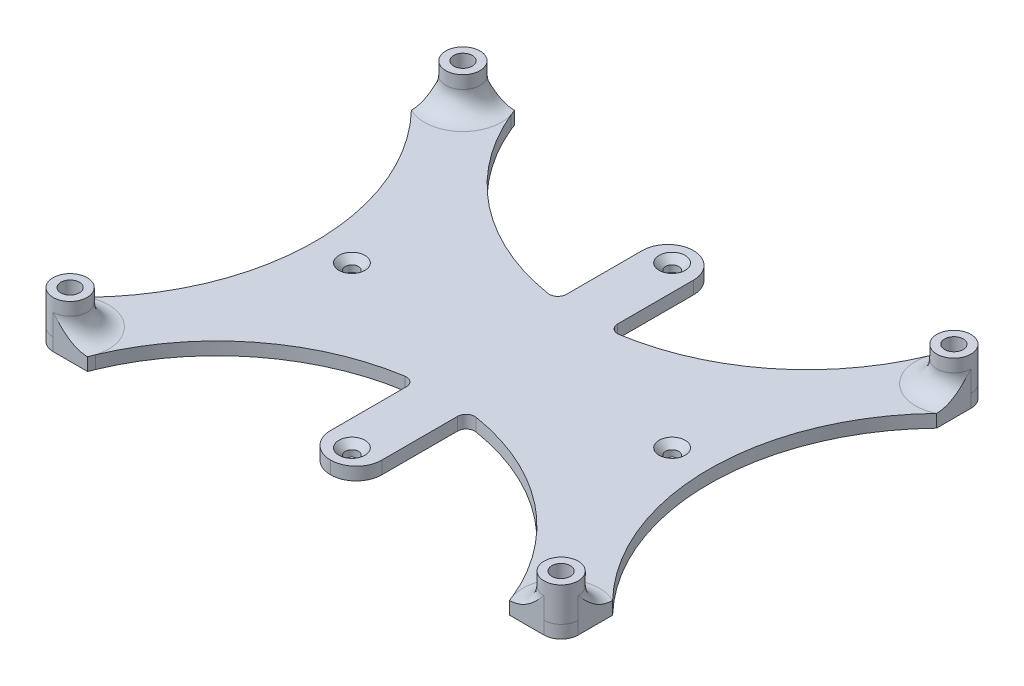
SolidWorks part; units mm, degrees
ref_plane "Alzado" through (0, 0, 0) normal (0, 0, 1) x (1, 0, 0)
ref_plane "Planta" through (0, 0, 0) normal (0, 1, 0) x (1, 0, 0)
ref_plane "Vista lateral" through (0, 0, 0) normal (1, 0, 0) x (0, 0, -1)
sketch "Croquis1" plane through (0, 0, 0) normal (0, 1, 0) x (1, 0, 0)
  line L1 (0, 0) -> (123, 0)
  line L2 (0, 0) -> (0, 100)
  line L3 (0, 100) -> (123, 100)
  line L4 (123, 0) -> (123, 100)
  dimension "D1" = 123
  dimension "D2" = 100
extrude "Saliente-Extruir1" add sketch "Croquis1" along normal blind 3
sketch "Croquis2" plane through (0, 3, 0) normal (0, 1, 0) x (1, 0, 0)
  line L0 (61.5, 100) -> (61.5, 0) construction
  line L1 (123, 100) -> (0, 100) construction
  line L2 (0, 0) -> (123, 0) construction
  line L3 (123, 0) -> (123, 100) construction
  line L4 (4, 4) -> (119, 4) construction
  line L5 (4, 4) -> (4, 96) construction
  line L6 (4, 96) -> (119, 96) construction
  line L7 (119, 4) -> (119, 96) construction
  line L8 (4, 4) -> (119, 96) construction
  line L9 (4, 96) -> (119, 4) construction
  circle A0 centre (4, 96) radius 4
  circle A1 centre (4, 4) radius 4
  circle A2 centre (119, 4) radius 4
  circle A3 centre (119, 96) radius 4
  point P6 (61.5, 50)
  dimension "D1" = 115
  dimension "D2" = 92
extrude "Saliente-Extruir2" add sketch "Croquis2" along normal blind 8
sketch "Croquis3" plane through (0, 11, 0) normal (0, 1, 0) x (1, 0, 0)
  circle A0 centre (4, 4) radius 4 construction
  circle A1 centre (4, 96) radius 4
  circle A2 centre (4, 96) radius 4
  arc A3 (123, 4) -> (119, 0) centre (119, 4) ccw construction
  arc A4 (119, 100) -> (123, 96) centre (119, 96) ccw construction
  circle A5 centre (4, 4) radius 4
  arc A6 (123, 4) -> (119, 0) centre (119, 4) ccw
  arc A7 (119, 100) -> (123, 96) centre (119, 96) ccw
  circle A8 centre (4, 96) radius 2.175
  circle A9 centre (119, 96) radius 2.175
  circle A10 centre (119, 4) radius 2.175
  circle A11 centre (4, 4) radius 2.175
  dimension "D2" = 4.35
  dimension "D1" = 0
extrude "Cortar-Extruir1" cut sketch "Croquis3" against normal blind 4.5 contours A8 | A9 | A10 | A11 region at (4, 11, -96) region at (119, 11, -96) region at (119, 11, -4) region at (4, 11, -4)
fillet "Redondeo1" radius 4 4 edges at (0, 1.5, -100) (123, 1.5, -100) (123, 1.5, 0) (0, 1.5, 0)
fillet "Redondeo2" radius 5 4 edges at (116.1716, 3, -6.8284) (116.1716, 3, -93.1716) (6.8284, 3, -93.1716) (6.8284, 3, -6.8284)
sketch "Croquis4" plane through (0, 3, 0) normal (0, 1, 0) x (1, 0, 0)
  line L0 (0, 50) -> (123, 50) construction
  line L1 (0, 87.9377) -> (0, 12.0623) construction
  line L2 (123, 12.0623) -> (123, 87.9377) construction
  line L3 (61.5, 50) -> (61.5, 0) construction
  line L4 (12.0623, 0) -> (110.9377, 0) construction
  line L5 (61.5, 50) -> (61.5, 100) construction
  line L6 (110.9377, 100) -> (12.0623, 100) construction
  circle A0 centre (24, 50) radius 1.55
  circle A1 centre (99, 50) radius 1.55
  circle A2 centre (61.5, 12.5) radius 1.55
  circle A3 centre (61.5, 87.5) radius 1.55
  dimension "D2" = 3.1
  dimension "D1" = 75
  dimension "D3" = 24
  dimension "D4" = 75
  dimension "D5" = 12.5
extrude "Cortar-Extruir2" cut sketch "Croquis4" against normal up to surface (3 mm away) up to face at (61.5, 0, -50)
sketch "Croquis5" plane through (0, 3, 0) normal (0, 1, 0) x (1, 0, 0)
  line L0 (0, 87.9377) -> (0, 12.0623)
  line L1 (12.0623, 100) -> (110.9377, 100)
  line L2 (61.5, 100) -> (61.5, 0) construction
  line L3 (12.0623, 0) -> (110.9377, 0) construction
  line L4 (0, 50) -> (123, 50) construction
  line L5 (123, 12.0623) -> (123, 87.9377) construction
  line L6 (123, 87.9377) -> (123, 12.0623)
  line L7 (12.0623, 0) -> (110.9377, 0)
  line L9 (67.5, 7.5) -> (55.5, 7.5)
  line L10 (67.5, 7.5) -> (67.5, 92.5)
  line L11 (67.5, 92.5) -> (55.5, 92.5)
  line L12 (55.5, 7.5) -> (55.5, 92.5)
  arc A0 (12.0623, 100) -> (55.5, 66.4541) centre (61.5, 119.1195) ccw
  arc A1 (0, 87.9377) -> (0, 12.0623) centre (-39.2296, 50) cw
  arc A2 (123, 87.9377) -> (123, 12.0623) centre (162.2296, 50) ccw
  arc A3 (12.0623, 0) -> (55.5, 33.5459) centre (61.5, -19.1195) cw
  circle A4 centre (61.5, 12.5) radius 1.55 construction
  circle A5 centre (61.5, 87.5) radius 1.55 construction
  arc A6 (67.5, 33.5459) -> (110.9377, 0) centre (61.5, -19.1195) cw
  arc A7 (67.5, 66.4541) -> (110.9377, 100) centre (61.5, 119.1195) ccw
  line M11 (12.0623, 0) -> (110.9377, 0)
  arc M12 (110.9377, 0) -> (123, 12.0623) centre (119, 4) cw
  line M13 (123, 12.0623) -> (123, 87.9377)
  arc M14 (123, 87.9377) -> (110.9377, 100) centre (119, 96) cw
  line M15 (110.9377, 100) -> (12.0623, 100)
  arc M16 (12.0623, 100) -> (0, 87.9377) centre (4, 96) cw
  line M17 (0, 87.9377) -> (0, 12.0623)
  arc M18 (0, 12.0623) -> (12.0623, 0) centre (4, 4) cw
  dimension "D3" = 5
  dimension "D4" = 5
  dimension "D1" = 12
  dimension "D2" = 6
chamfer "Chaflán1" distance 1.5 angle 45 4 edges at (99, 3, -48.45) (24, 3, -48.45) (61.5, 3, -85.95) (61.5, 3, -10.95)
extrude "Cortar-Extruir3" cut sketch "Croquis5" against normal blind 10 contours A6 L10 L9 L12 A3 M18 M11 M12 | A1 M17 | A2 M13 | L10 A7 A0 L12 L11 M14 M15 M16 region at (6.218, 3, -50) region at (13.319, 3, -99.747) region at (30.2883, 3, -22.4242) region at (116.782, 3, -50)
fillet "Redondeo3" radius 6 4 edges at (67.5, 1.5, -92.5) (55.5, 1.5, -92.5) (55.5, 1.5, -7.5) (67.5, 1.5, -7.5)
fillet "Redondeo4" radius 2 4 edges at (67.5, 1.5, -33.5459) (55.5, 1.5, -33.5459) (55.5, 1.5, -66.4541) (67.5, 1.5, -66.4541)
